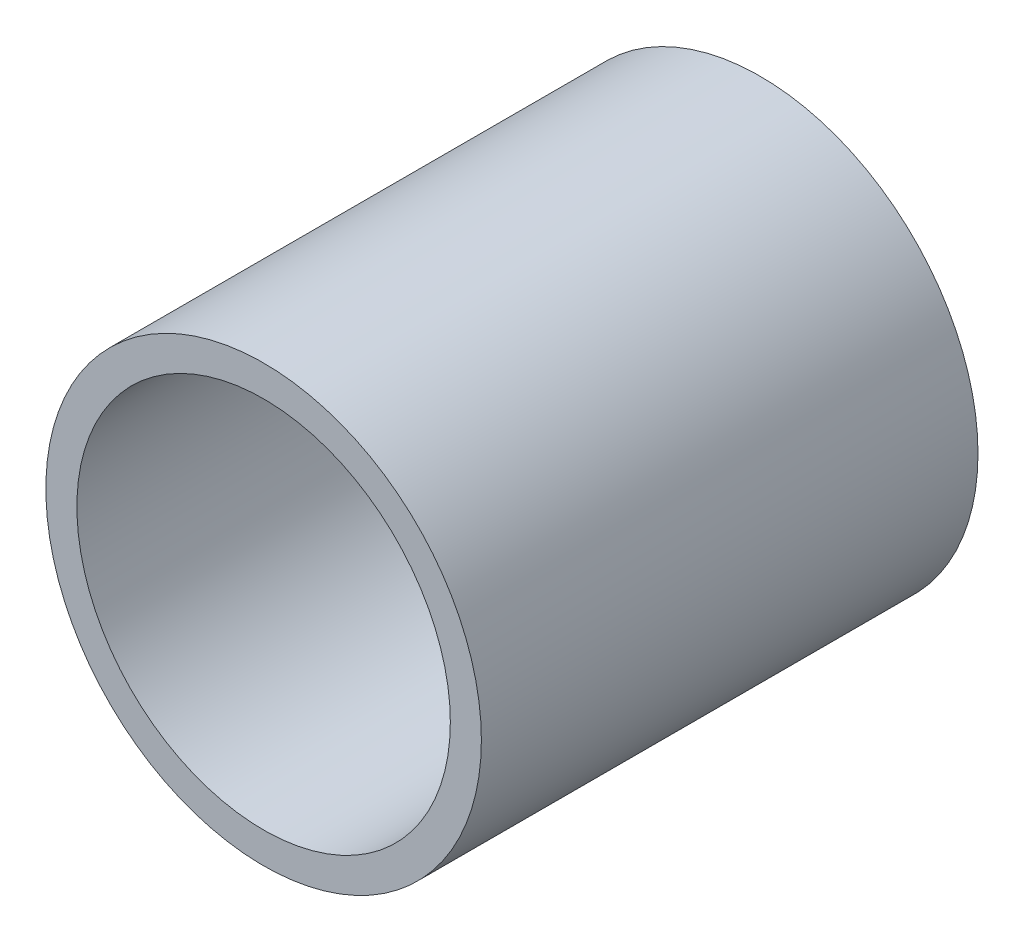
SolidWorks part; units mm, degrees
ref_plane "Front Plane" through (0, 0, 0) normal (0, 0, 1) x (1, 0, 0)
ref_plane "Top Plane" through (0, 0, 0) normal (0, 1, 0) x (1, 0, 0)
ref_plane "Right Plane" through (0, 0, 0) normal (1, 0, 0) x (0, 0, -1)
sketch "Sketch1" plane through (0, 0, 0) normal (0, 0, 1) x (1, 0, 0)
  circle A0 centre (0, 0) radius 11.1379
  circle A1 centre (0, 0) radius 9.5504
  dimension "OD" = 22.2758
  dimension "ID" = 19.1008
sketch "Sketch2" plane through (0, 0, 0) normal (1, 0, 0) x (0, 0, -1)
  line L2 (12.7, 0) -> (-12.7, 0) construction
  line L4 (-12.7, -11.1379) -> (-12.7, 11.1379) construction
  line L5 (-12.7, -9.5504) -> (12.7, -9.5504)
  line L6 (12.7, 9.5504) -> (-12.7, 9.5504)
  line L7 (12.7, -11.1379) -> (12.7, 11.1379) construction
  line L8 (-12.7, 11.1379) -> (12.7, 11.1379) construction
  line L9 (-12.7, -11.1379) -> (12.7, -11.1379) construction
  line L10 (0, 11.1379) -> (0, -11.1379) construction
  line L11 (0, 9.5504) -> (0, -9.5504) construction
  point P4 (0, -9.5504)
  point P7 (0, 9.5504)
  point P8 (0, 0)
  point P12 (-12.7, 0)
  point P15 (12.7, 0)
  point P16 (0, -11.1379)
  point P17 (0, 11.1379)
  dimension "Length" = 25.4
sketch "Sketch5" plane through (0, 0, 0) normal (0, 0, 1) x (1, 0, 0)
  circle A1 centre (0, 0) radius 9.5504
  circle A2 centre (0, 0) radius 9.5504
  circle A3 centre (0, 0) radius 11.1379
  circle A4 centre (0, 0) radius 11.1379
  dimension "D1" = 0
  dimension "D2" = 0
extrude "Boss-Extrude1" add sketch "Sketch5" along normal up to vertex and the other way up to vertex up to point (0, 0, 12.7) other way up to point (0, 0, -12.7)
sketch "Sketch4" plane through (0, 0, 12.7) normal (0, 0, 1) x (1, 0, 0)
  line L0 (0, 0) -> (-6.7532, 6.7532)
  line L2 (0, -11.1379) -> (0, 11.1379) construction
  circle A1 centre (0, 0) radius 9.5504 construction
  dimension "D1" = 45
equation "\"D1\"= \"Length@Sketch2\""
